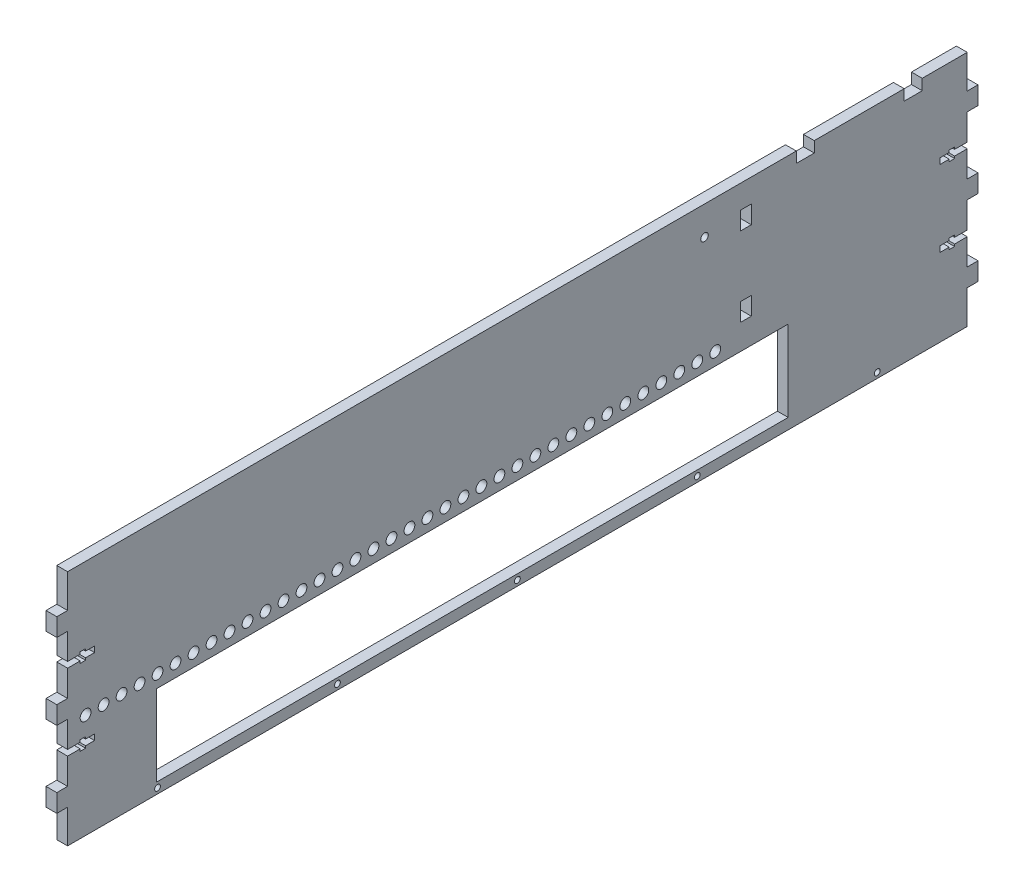
SolidWorks part; units mm, degrees
ref_plane "Front Plane" through (0, 0, 0) normal (0, 0, 1) x (1, 0, 0)
ref_plane "Top Plane" through (0, 0, 0) normal (0, 1, 0) x (1, 0, 0)
ref_plane "Right Plane" through (0, 0, 0) normal (1, 0, 0) x (0, 0, -1)
sketch "Sketch1" plane through (0, 0, 0) normal (1, 0, 0) x (0, 0, -1)
  line L1 (-250, -66) -> (250, -66)
  line L2 (-250, -66) -> (-250, 66)
  line L3 (-250, 66) -> (250, 66)
  line L4 (250, -66) -> (250, 66)
  line L5 (-250, -66) -> (250, 66) construction
  line L6 (-250, 66) -> (250, -66) construction
  point P0 (0, 0)
  dimension "D1" = 132
  dimension "D2" = 500
extrude "Boss-Extrude1" add sketch "Sketch1" along normal blind 6
sketch "Sketch4" plane through (0, 0, 250) normal (0, 0, 1) x (1, 0, 0)
  line L0 (0, 66) -> (0, -66) construction
  line L1 (0, 47.3321) -> (6, 47.3321)
  line L2 (0, 47.3321) -> (0, 37.3321)
  line L3 (0, 37.3321) -> (6, 37.3321)
  line L4 (6, 47.3321) -> (6, 37.3321)
  line L5 (6, 66) -> (6, -66) construction
  line L6 (0, 37.3321) -> (6, 37.3321) construction
  line L7 (0, -66) -> (0, 66) construction
  line L8 (6, 47.3321) -> (0, 47.3321) construction
  line L9 (0, -5) -> (6, -5) construction
  line L10 (0, -5) -> (6, -5)
  line L11 (0, -5) -> (0, 5)
  line L12 (0, 5) -> (6, 5)
  line L13 (6, -5) -> (6, 5)
  line L14 (6, -66) -> (6, 66) construction
  line L15 (6, 5) -> (0, 5) construction
  line L16 (6, -37.3321) -> (0, -37.3321) construction
  line L17 (0, -47.3321) -> (6, -47.3321)
  line L18 (0, -47.3321) -> (0, -37.3321)
  line L19 (0, -37.3321) -> (6, -37.3321)
  line L20 (6, -47.3321) -> (6, -37.3321)
  line L21 (0, -47.3321) -> (6, -47.3321) construction
extrude "Boss-Extrude2" add sketch "Sketch4" along normal blind 6
sketch "Sketch5" plane through (0, 0, 0) normal (-1, 0, 0) x (0, 0, 1)
  line L0 (250, 37.3321) -> (250, 5) construction
  line L1 (250, 5) -> (250, -5) construction
  line L2 (250, -5) -> (250, -37.3321) construction
  line L3 (250, 21.1661) -> (235, 21.1661) construction
  line L4 (240, -23.9661) -> (243, -18.3661) construction
  line L5 (250, 22.7661) -> (235, 22.7661)
  line L6 (240, -18.3661) -> (243, -23.9661) construction
  line L7 (250, 19.5661) -> (235, 19.5661)
  line L8 (250, -21.1661) -> (235, -21.1661) construction
  line L9 (250, 22.7661) -> (250, 19.5661)
  line L10 (235, 22.7661) -> (235, 19.5661)
  line L11 (243, -18.3661) -> (243, -23.9661)
  line L12 (240, -23.9661) -> (243, -23.9661)
  line L13 (250, 0) -> (222.8268, 0) construction
  line L14 (240, 18.3661) -> (243, 18.3661)
  line L15 (240, 18.3661) -> (240, 23.9661)
  line L16 (240, 23.9661) -> (243, 23.9661)
  line L17 (243, 18.3661) -> (243, 23.9661)
  line L18 (240, 18.3661) -> (243, 23.9661) construction
  line L19 (240, 23.9661) -> (243, 18.3661) construction
  line L20 (240, -18.3661) -> (240, -23.9661)
  line L21 (240, -18.3661) -> (243, -18.3661)
  line L22 (235, -22.7661) -> (235, -19.5661)
  line L23 (250, -22.7661) -> (250, -19.5661)
  line L24 (250, -19.5661) -> (235, -19.5661)
  line L25 (250, -22.7661) -> (235, -22.7661)
  point P20 (241.5, 21.1661)
  point P29 (241.5, -21.1661)
  dimension "D3" = 15
  dimension "D4" = 7
  dimension "D5" = 3
  dimension "D6" = 5.6
  dimension "D1" = 1.6
  dimension "D2" = 1.6
extrude "Cut-Extrude3" cut sketch "Sketch5" against normal up to next contours L17 L7 L9 L5 | L7 L17 L5 L15 | L5 L17 L16 L15 | L14 L17 L7 L15 | L7 L15 L5 L10 | L25 L23 L24 L11 | L25 L11 L24 L20 | L24 L11 L21 L20 | L11 L25 L20 L12 | L25 L20 L24 L22 region at (0, 21.1661, 246.5) region at (0, 21.1661, 241.5) region at (0, 23.3661, 241.5) region at (0, 21.1661, 237.5) region at (0, 18.9661, 241.5) region at (0, -18.9661, 241.5) region at (0, -21.1661, 246.5) region at (0, -21.1661, 241.5) region at (0, -23.3661, 241.5) region at (0, -21.1661, 237.5)
sketch "Sketch6" plane through (0, 0, -250) normal (0, 0, -1) x (-1, 0, 0)
  line L0 (0, 47.3321) -> (0, 37.3321) construction
  line L1 (0, 37.3321) -> (-6, 37.3321) construction
  line L2 (-6, 37.3321) -> (-6, 47.3321) construction
  line L3 (-6, 47.3321) -> (0, 47.3321) construction
  line L4 (0, 5) -> (0, -5) construction
  line L5 (0, -5) -> (-6, -5) construction
  line L6 (-6, -5) -> (-6, 5) construction
  line L7 (-6, 5) -> (0, 5) construction
  line L8 (0, -37.3321) -> (0, -47.3321) construction
  line L9 (0, -47.3321) -> (-6, -47.3321) construction
  line L10 (-6, -47.3321) -> (-6, -37.3321) construction
  line L11 (-6, -37.3321) -> (0, -37.3321) construction
  line L12 (0, 47.3321) -> (0, 37.3321)
  line L13 (0, 37.3321) -> (-6, 37.3321)
  line L14 (-6, 37.3321) -> (-6, 47.3321)
  line L15 (-6, 47.3321) -> (0, 47.3321)
  line L16 (0, 5) -> (0, -5)
  line L17 (0, -5) -> (-6, -5)
  line L18 (-6, -5) -> (-6, 5)
  line L19 (-6, 5) -> (0, 5)
  line L20 (0, -37.3321) -> (0, -47.3321)
  line L21 (0, -47.3321) -> (-6, -47.3321)
  line L22 (-6, -47.3321) -> (-6, -37.3321)
  line L23 (-6, -37.3321) -> (0, -37.3321)
extrude "Boss-Extrude3" add sketch "Sketch6" along normal blind 6
sketch "Sketch7" plane through (0, 0, 0) normal (-1, 0, 0) x (0, 0, 1)
  line L0 (0, 0) -> (0, -63.2146) construction
  line L1 (240, 22.7661) -> (240, 23.9661) construction
  line L2 (240, 22.7661) -> (235, 22.7661) construction
  line L3 (235, 22.7661) -> (235, 19.5661) construction
  line L4 (240, 19.5661) -> (235, 19.5661) construction
  line L5 (240, 18.3661) -> (240, 19.5661) construction
  line L6 (240, 18.3661) -> (243, 18.3661) construction
  line L7 (243, 18.3661) -> (243, 19.5661) construction
  line L8 (250, 19.5661) -> (243, 19.5661) construction
  line L9 (250, 22.7661) -> (243, 22.7661) construction
  line L10 (240, 23.9661) -> (243, 23.9661) construction
  line L11 (243, 22.7661) -> (243, 23.9661) construction
  line L12 (240, 22.7661) -> (235, 22.7661) construction
  line L13 (235, 22.7661) -> (235, 19.5661) construction
  line L14 (240, 19.5661) -> (235, 19.5661) construction
  line L15 (240, 18.3661) -> (240, 19.5661) construction
  line L16 (240, 18.3661) -> (243, 18.3661) construction
  line L17 (243, 18.3661) -> (243, 19.5661) construction
  line L18 (250, 19.5661) -> (243, 19.5661) construction
  line L19 (250, 22.7661) -> (243, 22.7661) construction
  line L20 (240, 23.9661) -> (243, 23.9661) construction
  line L21 (243, 22.7661) -> (243, 23.9661) construction
  line L22 (240, 22.7661) -> (240, 23.9661) construction
  line L23 (250, -19.5661) -> (243, -19.5661) construction
  line L24 (240, -18.3661) -> (243, -18.3661) construction
  line L25 (243, -18.3661) -> (243, -19.5661) construction
  line L26 (240, -18.3661) -> (240, -19.5661) construction
  line L27 (240, -19.5661) -> (235, -19.5661) construction
  line L28 (235, -22.7661) -> (235, -19.5661) construction
  line L29 (240, -22.7661) -> (235, -22.7661) construction
  line L30 (240, -22.7661) -> (240, -23.9661) construction
  line L31 (240, -23.9661) -> (243, -23.9661) construction
  line L32 (243, -22.7661) -> (243, -23.9661) construction
  line L33 (250, -22.7661) -> (243, -22.7661) construction
  line L34 (250, -19.5661) -> (243, -19.5661) construction
  line L35 (240, -18.3661) -> (243, -18.3661) construction
  line L36 (243, -18.3661) -> (243, -19.5661) construction
  line L37 (240, -18.3661) -> (240, -19.5661) construction
  line L38 (240, -19.5661) -> (235, -19.5661) construction
  line L39 (235, -22.7661) -> (235, -19.5661) construction
  line L40 (240, -22.7661) -> (235, -22.7661) construction
  line L41 (240, -22.7661) -> (240, -23.9661) construction
  line L42 (240, -23.9661) -> (243, -23.9661) construction
  line L43 (243, -22.7661) -> (243, -23.9661) construction
  line L44 (250, -22.7661) -> (243, -22.7661) construction
  line L45 (250, 22.7661) -> (250, 19.5661) construction
  line L46 (250, -19.5661) -> (250, -22.7661) construction
  line L47 (-250, -19.5661) -> (-250, -22.7661)
  line L48 (-250, 22.7661) -> (-250, 19.5661)
  line L49 (-250, -22.7661) -> (-243, -22.7661)
  line L50 (-243, -22.7661) -> (-243, -23.9661)
  line L51 (-240, -23.9661) -> (-243, -23.9661)
  line L52 (-240, -22.7661) -> (-240, -23.9661)
  line L53 (-240, -22.7661) -> (-235, -22.7661)
  line L54 (-235, -22.7661) -> (-235, -19.5661)
  line L55 (-240, -19.5661) -> (-235, -19.5661)
  line L56 (-240, -18.3661) -> (-240, -19.5661)
  line L57 (-243, -18.3661) -> (-243, -19.5661)
  line L58 (-240, -18.3661) -> (-243, -18.3661)
  line L59 (-250, -19.5661) -> (-243, -19.5661)
  line L60 (-240, 22.7661) -> (-240, 23.9661)
  line L61 (-243, 22.7661) -> (-243, 23.9661)
  line L62 (-240, 23.9661) -> (-243, 23.9661)
  line L63 (-250, 22.7661) -> (-243, 22.7661)
  line L64 (-250, 19.5661) -> (-243, 19.5661)
  line L65 (-243, 18.3661) -> (-243, 19.5661)
  line L66 (-240, 18.3661) -> (-243, 18.3661)
  line L67 (-240, 18.3661) -> (-240, 19.5661)
  line L68 (-240, 19.5661) -> (-235, 19.5661)
  line L69 (-235, 22.7661) -> (-235, 19.5661)
  line L70 (-240, 22.7661) -> (-235, 22.7661)
extrude "Cut-Extrude4" cut sketch "Sketch7" against normal up to next
sketch "Sketch8" plane through (0, 0, 0) normal (-1, 0, 0) x (0, 0, 1)
  line L0 (200, -15.55) -> (-150, -15.55) construction
  line L1 (200, -15.55) -> (-150, -15.55) construction
  line L2 (200, -15.55) -> (200, -60) construction
  line L3 (200, -15.55) -> (200, -60) construction
  line L186 (-150, -15.55) -> (-150, -60) construction
  line L187 (-150, -60) -> (200, -60) construction
  line L188 (200.5, -15.05) -> (200.5, -60)
  line L189 (200.5, -15.05) -> (-150.5, -15.05)
  line L190 (-150.5, -15.05) -> (-150.5, -60)
  line L191 (-150.5, -60) -> (200.5, -60)
  dimension "D1" = 0.5
extrude "Cut-Extrude5" cut sketch "Sketch8" against normal up to next
sketch "Sketch10" plane through (6, 0, 0) normal (1, 0, 0) x (0, 0, -1)
  line L0 (0, 0) -> (0, -66) construction
  line L1 (-250, -66) -> (250, -66) construction
  line L2 (0, -63) -> (250, -63) construction
  line L3 (250, -66) -> (250, -47.3321) construction
  circle A0 centre (0, -63) radius 1.6
  circle A1 centre (100, -63) radius 1.6
  circle A2 centre (200, -63) radius 1.6
  circle A3 centre (-100, -63) radius 1.6
  circle A4 centre (-200, -63) radius 1.6
  dimension "D2" = 3.2
  dimension "D1" = 3
  dimension "D3" = 100
  dimension "D4" = 100
extrude "Cut-Extrude7" cut sketch "Sketch10" against normal up to next
sketch "Sketch11" plane through (6, 0, 0) normal (1, 0, 0) x (0, 0, -1)
  line L0 (130, 43) -> (130, 53) construction
  line L1 (130, 53) -> (124, 53) construction
  line L2 (124, 53) -> (124, 43) construction
  line L3 (124, 43) -> (130, 43) construction
  line L4 (130, -1) -> (130, 9) construction
  line L5 (130, 9) -> (124, 9) construction
  line L6 (124, 9) -> (124, -1) construction
  line L7 (124, -1) -> (130, -1) construction
  line L8 (130, 43) -> (130, 53)
  line L9 (130, 53) -> (124, 53)
  line L10 (124, 53) -> (124, 43)
  line L11 (124, 43) -> (130, 43)
  line L12 (130, -1) -> (130, 9)
  line L13 (130, 9) -> (124, 9)
  line L14 (124, 9) -> (124, -1)
  line L15 (124, -1) -> (130, -1)
extrude "Cut-Extrude8" cut sketch "Sketch11" against normal up to next
sketch "Sketch12" plane through (0, 0, 0) normal (-1, 0, 0) x (0, 0, 1)
  line L0 (-124, 53) -> (-124, 43) construction
  line L1 (-250, 66) -> (250, 66) construction
  circle A0 centre (-104, 50) radius 2.1
  dimension "D1" = 20
  dimension "D3" = 4.2
  dimension "D2" = 16
extrude "Cut-Extrude9" cut sketch "Sketch12" against normal up to next
sketch "Sketch13" plane through (0, 66, 0) normal (0, 1, 0) x (1, 0, 0)
  line L0 (6, 250) -> (6, -250) construction
  line L1 (0, 215) -> (6, 215)
  line L2 (0, 215) -> (0, 225)
  line L3 (0, 225) -> (6, 225)
  line L4 (6, 215) -> (6, 225)
  line L5 (0, 215) -> (6, 225) construction
  line L6 (0, 225) -> (6, 215) construction
  line L7 (6, 225) -> (0, 225) construction
  line L8 (6, 165) -> (0, 165) construction
  line L9 (0, 155) -> (6, 155)
  line L10 (0, 155) -> (0, 165)
  line L11 (0, 165) -> (6, 165)
  line L12 (6, 155) -> (6, 165)
  line L13 (0, 155) -> (6, 165) construction
  line L14 (0, 165) -> (6, 155) construction
  point P0 (3, 220)
  point P10 (3, 160)
extrude "Cut-Extrude10" cut sketch "Sketch13" against normal blind 6
sketch "Sketch14" plane through (0, 0, 0) normal (-1, 0, 0) x (0, 0, 1)
  circle A0 centre (240, -8) radius 3 construction
  circle A1 centre (240, -8) radius 3
  circle A2 centre (230, -8) radius 3
  circle A3 centre (220, -8) radius 3
  circle A4 centre (210, -8) radius 3
  circle A5 centre (200, -8) radius 3
  circle A6 centre (190, -8) radius 3
  circle A7 centre (180, -8) radius 3
  circle A8 centre (170, -8) radius 3
  circle A9 centre (160, -8) radius 3
  circle A10 centre (150, -8) radius 3
  circle A11 centre (140, -8) radius 3
  circle A12 centre (130, -8) radius 3
  circle A13 centre (120, -8) radius 3
  circle A14 centre (110, -8) radius 3
  circle A15 centre (100, -8) radius 3
  circle A16 centre (90, -8) radius 3
  circle A17 centre (80, -8) radius 3
  circle A18 centre (70, -8) radius 3
  circle A19 centre (60, -8) radius 3
  circle A20 centre (50, -8) radius 3
  circle A21 centre (40, -8) radius 3
  circle A22 centre (30, -8) radius 3
  circle A23 centre (20, -8) radius 3
  circle A24 centre (10, -8) radius 3
  circle A25 centre (0, -8) radius 3
  circle A26 centre (-10, -8) radius 3
  circle A27 centre (-20, -8) radius 3
  circle A28 centre (-30, -8) radius 3
  circle A29 centre (-40, -8) radius 3
  circle A30 centre (-50, -8) radius 3
  circle A31 centre (-60, -8) radius 3
  circle A32 centre (-70, -8) radius 3
  circle A33 centre (-80, -8) radius 3
  circle A34 centre (-90, -8) radius 3
  circle A35 centre (-100, -8) radius 3
  circle A36 centre (-110, -8) radius 3
  dimension "D1" = 36
extrude "Cut-Extrude11" cut sketch "Sketch14" against normal up to next (6 mm away)
